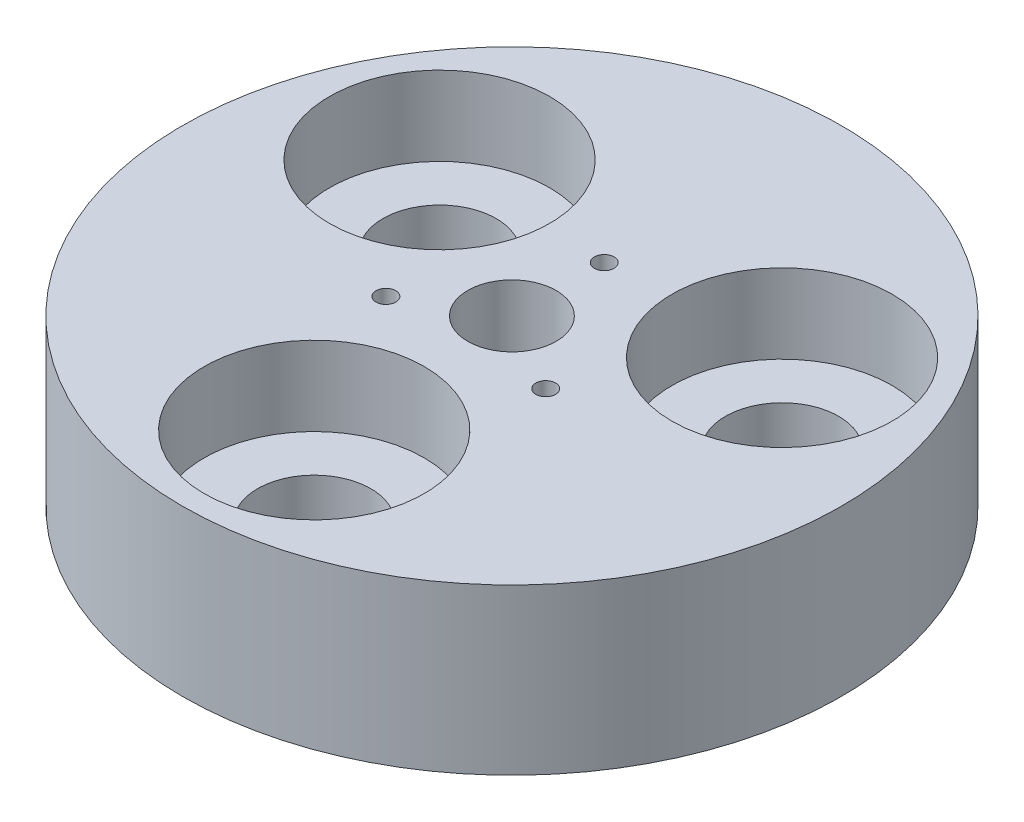
SolidWorks part; units mm, degrees
material "ABS"
ref_plane "Front Plane" through (0, 0, 0) normal (0, 0, 1) x (1, 0, 0)
ref_plane "Top Plane" through (0, 0, 0) normal (0, 1, 0) x (1, 0, 0)
ref_plane "Right Plane" through (0, 0, 0) normal (1, 0, 0) x (0, 0, -1)
sketch "Sketch1" plane through (0, 0, 0) normal (0, 1, 0) x (1, 0, 0)
  circle A0 centre (0, 0) radius 6.35
  dimension "D1" = 12.7
extrude "Boss-Extrude1" add sketch "Sketch1" along normal blind 3.175 contours A0
ref_axis "Axis1" through (0, 3.175, 0) along (0, -1, 0)
sketch "Sketch5" plane through (0, 3.175, 0) normal (0, 1, 0) x (1, 0, 0)
  circle A0 centre (0, 1.778) radius 0.1905
  dimension "D1" = 0.381
  dimension "D2" = 1.778
extrude "Cut-Extrude3" cut sketch "Sketch5" against normal blind 1.905
pattern_circular "CirPattern3" count 3 over 360 about axis through (0, 3.175, 0) along (0, -1, 0) of "Cut-Extrude3"
sketch "Sketch6" plane through (0, 3.175, 0) normal (0, 1, 0) x (1, 0, 0)
  circle A0 centre (0, 0) radius 0.8509
  dimension "D1" = 1.7018
extrude "Cut-Extrude4" cut sketch "Sketch6" against normal up to surface (3.175 mm away) up to face at (0, 0, 6.35)
hole_wizard "CBORE for #2 Binding Head Machine Screw1" positions "Sketch7" profile "Sketch8" counterbore size "#2" standard "ANSI Inch" end condition through all
sketch "Sketch7" plane through (0, 3.175, 0) normal (0, 1, 0) x (1, 0, 0)
  point P0 (0, -3.81)
  dimension "D1" = 3.81
sketch "Sketch8" plane through (0, 3.175, 3.81) normal (1, 0, 0) x (0, 0, 1)
  line L0 (0, 0) -> (0, 3.175)
  line L1 (0, 3.175) -> (1.0922, 3.175)
  line L3 (1.0922, 3.175) -> (1.0922, 1.524)
  line L4 (1.0922, 1.524) -> (2.1209, 1.524)
  line L5 (2.1209, 1.524) -> (2.1209, 0)
  line L7 (2.1209, 0) -> (0, 0)
  line L11 (0, -6.35) -> (0, 107.95) construction
  dimension "Thru Hole Dia." = 2.1844
  dimension "Thru Hole Depth" = 3.175
  dimension "C'Bore Dia." = 4.2418
  dimension "C'Bore Depth" = 1.524
pattern_circular "CirPattern4" count 3 over 360 about axis through (0, 3.175, 0) along (0, -1, 0) of "CBORE for #2 Binding Head Machine Screw1"
